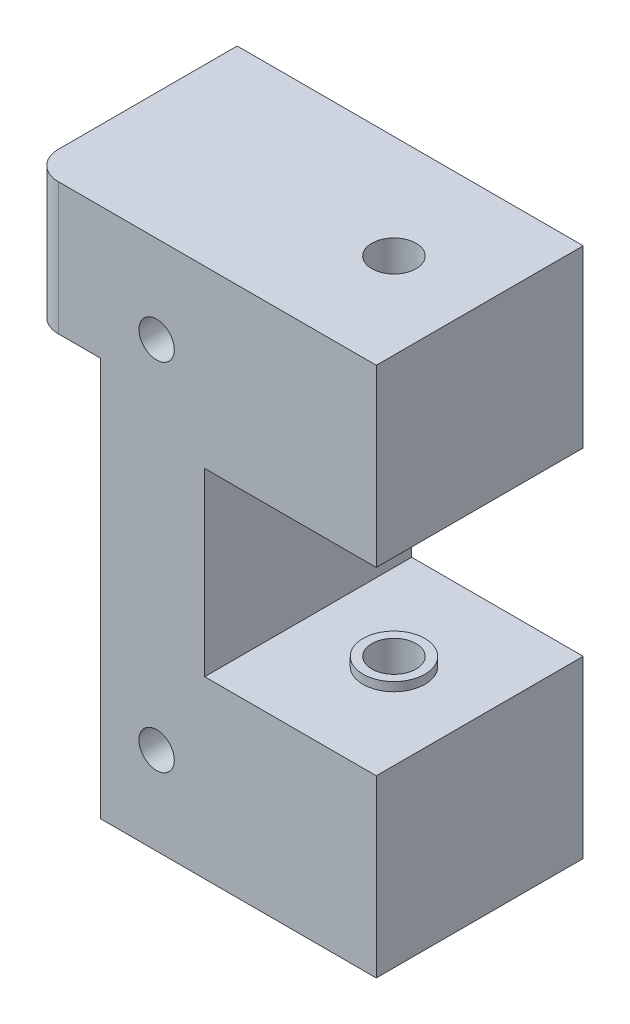
SolidWorks part; units mm, degrees
ref_plane "Front Plane" through (0, 0, 0) normal (0, 0, 1) x (1, 0, 0)
ref_plane "Top Plane" through (0, 0, 0) normal (0, 1, 0) x (1, 0, 0)
ref_plane "Right Plane" through (0, 0, 0) normal (1, 0, 0) x (0, 0, -1)
sketch "MainBlock" plane through (0, 0, 0) normal (0, 0, 1) x (1, 0, 0)
  line L0 (0, 0) -> (39.125, 0)
  line L1 (39.125, 0) -> (39.125, 19.8)
  line L2 (39.125, 19.8) -> (19.725, 19.8)
  line L3 (19.725, 19.8) -> (19.725, 40.2)
  line L4 (19.725, 40.2) -> (39.125, 40.2)
  line L5 (39.125, 40.2) -> (39.125, 60)
  line L6 (39.125, 60) -> (0, 60)
  line L7 (0, 60) -> (0, 0)
  circle A0 centre (14.2875, 50.1) radius 2
  circle A1 centre (14.2875, 9.9) radius 2
  dimension "D4" = 4
  dimension "D1" = 39.125
  dimension "D2" = 60
  dimension "D3" = 20.4
  dimension "D5" = 19.4
  dimension "D6" = 14.2875
  dimension "D7" = 9.9
  dimension "D8" = 9.9
  dimension "D9" = 19.8
  dimension "D10" = 19.8
extrude "MainBlockBoss-Extrude1" add sketch "MainBlock" along normal blind 23.4
sketch "TopHoleCut-Sketch2" plane through (0, 60, 0) normal (0, 1, 0) x (1, 0, 0)
  line L0 (39.125, 0) -> (0, 0) construction
  circle A0 centre (29.425, -11.7) radius 2.5
  dimension "D3" = 5
  dimension "D1" = 11.7
  dimension "D2" = 9.7
extrude "TopHoleCut-Extrude1" cut sketch "TopHoleCut-Sketch2" against normal blind 45
sketch "TopSpacerSketch4" plane through (0, 40.2, 0) normal (0, -1, 0) x (1, 0, 0)
  circle A0 centre (29.425, 11.7) radius 3.5
  circle A1 centre (29.425, 11.7) radius 2.5
  circle A2 centre (29.425, 11.7) radius 2.5 construction
  dimension "D1" = 7
extrude "TopSpacerBoss-Extrude2" add sketch "TopSpacerSketch4" along normal blind 1
sketch "LowerSpacerSketch5" plane through (0, 19.8, 0) normal (0, 1, 0) x (1, 0, 0)
  circle A0 centre (29.425, -11.7) radius 2.5
  circle A1 centre (29.425, -11.7) radius 2.5 construction
  circle A2 centre (29.425, -11.7) radius 3.5
  circle A3 centre (29.425, -11.7) radius 3.5 construction
extrude "LowerSpacerBoss-Extrude3" add sketch "LowerSpacerSketch5" along normal blind 1
sketch "MountHoleBoreSketch1" plane through (0, 0, 0) normal (0, 0, -1) x (-1, 0, 0)
  line L1 (-10.4125, 50.1) -> (-12.35, 53.4558)
  line L2 (-12.35, 53.4558) -> (-16.225, 53.4558)
  line L3 (-16.225, 53.4558) -> (-18.1625, 50.1)
  line L4 (-18.1625, 50.1) -> (-16.225, 46.7442)
  line L5 (-16.225, 46.7442) -> (-12.35, 46.7442)
  line L6 (-12.35, 46.7442) -> (-10.4125, 50.1)
  line L7 (-10.4125, 9.9) -> (-12.35, 13.2558)
  line L8 (-12.35, 13.2558) -> (-16.225, 13.2558)
  line L9 (-16.225, 13.2558) -> (-18.1625, 9.9)
  line L10 (-18.1625, 9.9) -> (-16.225, 6.5442)
  line L11 (-16.225, 6.5442) -> (-12.35, 6.5442)
  line L12 (-12.35, 6.5442) -> (-10.4125, 9.9)
  circle A0 centre (-14.2875, 50.1) radius 3.3558 construction
  circle A1 centre (-14.2875, 9.9) radius 3.3558 construction
  dimension "D1" = 7.75
extrude "MountHoleBoreCut-Extrude1" cut sketch "MountHoleBoreSketch1" against normal blind 2
sketch "PushPinHoleSketch1" plane through (0, 0, 0) normal (0, -1, 0) x (1, 0, 0)
  circle A0 centre (29.425, 11.7) radius 1
  circle A1 centre (29.425, 11.7) radius 2.5 construction
  dimension "D1" = 2
extrude "PushPinHoleCut-Extrude1" cut sketch "PushPinHoleSketch1" against normal through all
sketch "MidRailInsetSketch1" plane through (0, 0, 0) normal (0, 0, -1) x (-1, 0, 0)
  line L0 (0, 60) -> (0, 0) construction
  line L1 (0, 45.1) -> (-7.9375, 45.1)
  line L2 (0, 45.1) -> (0, 0)
  line L3 (0, 0) -> (-7.9375, 0)
  line L4 (-7.9375, 45.1) -> (-7.9375, 0)
  line L6 (0, 0) -> (-39.125, 0) construction
  line L7 (-39.125, 60) -> (0, 60) construction
  dimension "D1" = 7.9375
  dimension "D2" = 14.9
extrude "MidRailInsetCut-Extrude2" cut sketch "MidRailInsetSketch1" against normal through all
fillet "VerticalSupportFillet1" radius 3.175 1 edges at (0, 52.55, 23.4)
equation "\"BeltTensionerWidth\"= \"MidRailToAlignWithGantryBlock\" + \"BeltTensionerInnerWidth\" / 2 + \"RailThickness\""
equation "\"BeltTensionerHeight\"= 60mm"
equation "\"BeltTensionerDepth\"= \"BeltTensionerBackWallThickness\" + \"BeltTensionerInnerDepth\"'Equals 23.4"
equation "\"BeltTensionerInnerWidth\"= \"20TGT2PulleyDiameter\" + \"BeltTensionerSpaceBetweenPulleyAndWall\""
equation "\"BeltTensionerInnerHeight\"= \"20TGT2PulleyWidth\" * 2 + \"1mmSpacer\" * 3"
equation "\"BeltTensionerBackWallThickness\"= 4mm"
equation "\"BeltTensionerInnerDepth\"= \"20TGT2PulleyDiameter\" + \"BeltTensionerSpaceBetweenPulleyAndWall\""
equation "\"RailThickness\"= .125in'Spec"
equation "\"HoleOffsetFromEdge\"= \"RailThickness\" * 2.5"
equation "\"LinearGBWithRailDepth\"= 12.75mm'Spec"
equation "\"GABDistanceFromBackToFirstPulley\"= 13.5mm"
equation "\"MidRailToAlignWithGantryBlock\"= \"LinearGBWithRailDepth\" + \"GABDistanceFromBackToFirstPulley\"'All outside cogs must align"
equation "\"20TGT2PulleyDiameter\"= 17.9mm'Spec"
equation "\"BeltTensionerSpaceBetweenPulleyAndWall\"= 1.5mm"
equation "\"BeltTensionerMountingHoleDiameter\"= 4.0mm"
equation "\"BeltTensionerMountingHoleOffsetFromEdge\"= \"HoleOffsetFromEdge\" + \"RailThickness\" * 2"
equation "\"20TGT2PulleyWidth\"= 8.7mm'The STL of the Pulley in the diagram is a bit larger"
equation "\"1mmSpacer\"= 1mm"
equation "\"SteelShaft5mmHoleDiameter\"= 5mm"
equation "\"BeltTensionerMountingHoleOuterBoreDepth\"= 2mm"
equation "\"BeltTensionerMountingHoleOuterBoreDiameter\"= 7.75mm"
equation "\"7mmx1mmSpacerDiameter\"= 7mm"
equation "\"7mmx1mmSpacerHeight\"= 1mm"
equation "\"D1@MainBlock\" = \"BeltTensionerWidth\""
equation "\"D4@MainBlock\" = \"BeltTensionerMountingHoleDiameter\""
equation "\"D5@MainBlock\" = \"BeltTensionerInnerWidth\""
equation "\"D6@MainBlock\" = \"BeltTensionerMountingHoleOffsetFromEdge\""
equation "\"D7@MainBlock\"=\"BeltTensionerMountingHoleOffstFromTopOrBottom\""
equation "\"D8@MainBlock\"=\"BeltTensionerMountingHoleOffstFromTopOrBottom\""
equation "\"D1@MainBlockBoss-Extrude1\" = \"BeltTensionerDepth\""
equation "\"D1@TopHoleCut-Sketch2\" = \"BeltTensionerDepth\" / 2"
equation "\"D3@TopHoleCut-Sketch2\" = \"SteelShaft5mmHoleDiameter\""
equation "\"D1@TopSpacerSketch4\" = \"7mmx1mmSpacerDiameter\""
equation "\"D1@TopSpacerBoss-Extrude2\" = \"7mmx1mmSpacerHeight\""
equation "\"D1@LowerSpacerBoss-Extrude3\" = \"7mmx1mmSpacerHeight\""
equation "\"D1@MountHoleBoreSketch1\" = \"BeltTensionerMountingHoleOuterBoreDiameter\""
equation "\"D1@MountHoleBoreCut-Extrude1\" = \"BeltTensionerMountingHoleOuterBoreDepth\""
equation "\"SteelPinPushHoleDiameter\"= 2mm"
equation "\"D1@PushPinHoleSketch1\" = \"SteelPinPushHoleDiameter\""
equation "\"D2@TopHoleCut-Sketch2\"=\"BeltTensionerWidth\" - \"MidRailToAlignWithGantryBlock\" - \"RailThickness\""
equation "\"BeltTensionerMountingHoleOffstFromTopOrBottom\"= ( \"BeltTensionerHeight\" - \"BeltTensionerInnerHeight\" ) / 4"
equation "\"BeltTensionerSteelShaftHoleDepthFromTop\"= ( \"SteelShaftLength\" - \"BeltTensionerInnerHeight\" ) / 2 + ( \"BeltTensionerHeight\" - \"BeltTensionerInnerHeight\" ) / 2 + \"BeltTensionerInnerHeight\"'Equals 45"
equation "\"SteelShaftLength\"= 30mm"
equation "\"D1@TopHoleCut-Extrude1\"=\"BeltTensionerSteelShaftHoleDepthFromTop\""
equation "\"MidSideRailVerticalOffset\"= \"LinearRailWidth\" + 3mm'Allows space for RodStabilizer to attach to bottom of MidSideRail"
equation "\"LinearRailWidth\"= 12mm'Spec"
equation "\"D2@MidRailInsetSketch1\"=\"DistanceAboveMidSideRailToTopOfBeltTensioner\""
equation "\"DistanceAboveMidSideRailToTopOfBeltTensioner\"= \"VS ToTopOfBeltTensionerAlignedWithYAxisGantryBlockUpperPulley\" - \"V8 ToTopOfMidSideRail\"'Equals 14.9"
equation "\"DistanceFromBeltTensionerTopPulleyToBeltTensionerTop\"= \"7mmx1mmSpacerHeight\" + \"BeltTensionerTopHeight\"'Equals 20.8"
equation "\"BeltTensionerTopHeight\"= ( \"BeltTensionerHeight\" - \"BeltTensionerInnerHeight\" ) / 2'Equals 19.8"
equation "\"GABUpperHeight\"= 4mm"
equation "\"D3@MainBlock\"=\"BeltTensionerInnerHeight\""
equation "\"D9@MainBlock\"=\"BeltTensionerTopHeight\""
equation "\"LegHeight\"= 70mm'Space needed for PSU/Stepper/Electronics"
equation "\"V1 BottomOfLowerRail\"= \"LegHeight\""
equation "\"LowerEnclosureThickness\"= 5mm"
equation "\"StepperShaftLength\"= 24mm'Pulley will be attached to the end"
equation "\"ZAxisLeadScrewLength\"= 200mm"
equation "\"LM8UUHeight\"= 24mm'Spec"
equation "\"V2 ToBedAtTopOfZAxis\"= \"V1 BottomOfLowerRail\" - \"LowerEnclosureThickness\" + \"StepperShaftLength\" + \"ZAxisLeadScrewLength\" - \"LM8UUHeight\" / 2'Equals 277"
equation "\"BedToBuildPlateStandoffLength\"= 15mm"
equation "\"BuildPlateHeight\"= 8mm'Spec"
equation "\"V4 ToTopOfBuildPlate/HotEndTip\"= \"V2 ToBedAtTopOfZAxis\" + \"BedToBuildPlateStandoffLength\" + \"BuildPlateHeight\""
equation "\"HotEndToTopOfXAxisGB\"= 71.68487mm'Equals 71.68487. Measured after installed onto X-Axis linear rail guide block"
equation "\"LinearGBWidth\"= 27mm'Spec"
equation "\"TopOfGBToBottomOfLinearRail\"= \"LinearGBWidth\" / 2 + \"LinearRailWidth\" / 2'Equals 19.5"
equation "\"V5 ToBottomOfXAxisLinearRail\"= \"V4 ToTopOfBuildPlate/HotEndTip\" + \"HotEndToTopOfXAxisGB\" - \"TopOfGBToBottomOfLinearRail\"'Equals 352.18487"
equation "\"GABMidWallHeight\"= 28mm'Must equal 28 or changes alignment"
equation "\"GABLowerHeight\"= 4mm"
equation "\"GABHeight\"= \"GABLowerHeight\" + \"GABMidWallHeight\" + \"GABUpperHeight\""
equation "\"V6 ToMiddleOfYAxisGantryBlock\"= \"V5 ToBottomOfXAxisLinearRail\" - \"GABHeight\" / 2'Equals 334.18487"
equation "\"V8 ToTopOfMidSideRail\"= \"V6 ToMiddleOfYAxisGantryBlock\" + \"MidSideRailVerticalOffset\"'Equals 349.18487"
equation "\"VS ToTopOfBeltTensionerAlignedWithYAxisGantryBlockUpperPulley\"= \"V5 ToBottomOfXAxisLinearRail\" - \"DistanceFromXAxisLinearRailBottomAndTopOfGantryPulley\" + \"DistanceFromBeltTensionerTopPulleyToBeltTensionerTop\"'Equals 364.08487"
equation "\"GABRiserBossOffset\"= 0.4mm'Aligns Pulleys inside edges to be 2.5mm (.5mm apart top to bottom)"
equation "\"GABMidShortRiserHeight\"= \"GABMidWallHeight\" / 2 - \"20TGT2PulleyWidth\"'Equals 5.3"
equation "\"DistanceFromXAxisLinearRailBottomAndTopOfGantryPulley\"= \"GABUpperHeight\" + \"GABMidShortRiserHeight\" - \"GABRiserBossOffset\"'Equals 8.9"
equation "\"D1@VerticalSupportFillet1\"=\"RailThickness\""
equation "\"D1@MidRailInsetSketch1\"=\"HoleOffsetFromEdge\""
